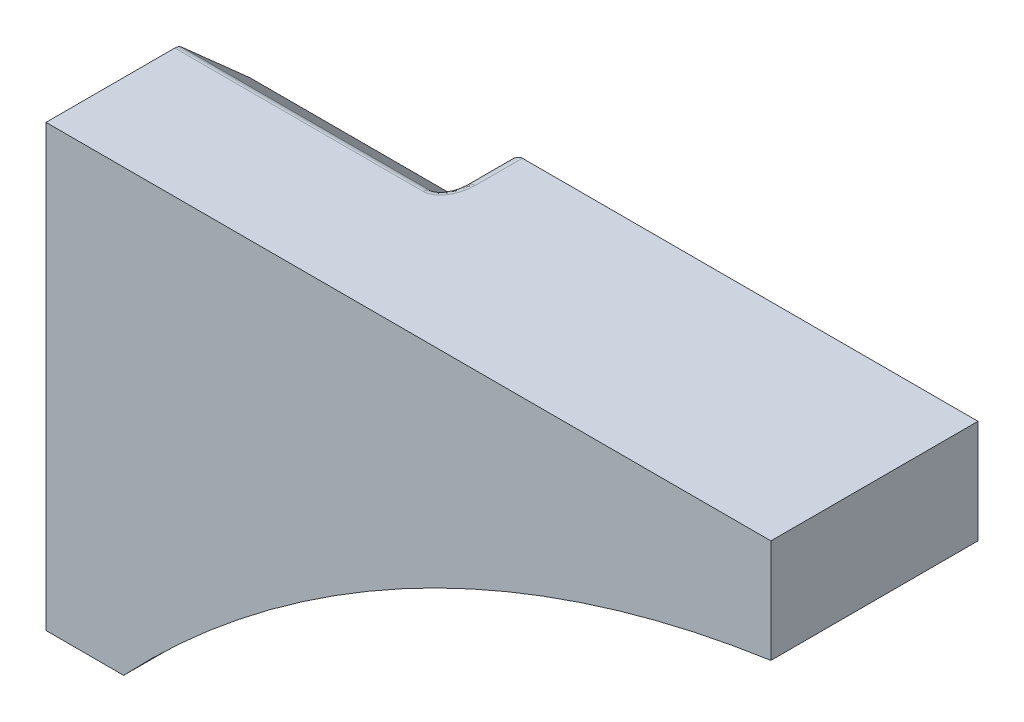
SolidWorks part; units mm, degrees
material "Nylon 101"
ref_plane "Front Plane" through (0, 0, 0) normal (0, 0, 1) x (1, 0, 0)
ref_plane "Top Plane" through (0, 0, 0) normal (0, 1, 0) x (1, 0, 0)
ref_plane "Right Plane" through (0, 0, 0) normal (1, 0, 0) x (0, 0, -1)
sketch "Sketch1" plane through (0, 0, 0) normal (0, 0, 1) x (1, 0, 0)
  line L0 (0, 0) -> (0, -107.95)
  line L2 (177.8, 0) -> (0, 0)
  line L3 (0, -107.95) -> (19.05, -107.95)
  line L5 (177.8, -25.4) -> (177.8, 0)
  line L6 (19.05, -107.95) -> (19.05, -25.4)
  line L7 (19.05, -25.4) -> (177.8, -25.4)
  dimension "D1" = 107.95
  dimension "D2" = 19.05
  dimension "D3" = 25.4
  dimension "D4" = 177.8
extrude "Boss-Extrude1" add sketch "Sketch1" along normal blind 50.8
sketch "Sketch2" plane through (0, 0, 0) normal (-1, 0, 0) x (0, 0, 1)
  line L0 (25.4, 0) -> (25.4, -107.95) construction
  line L1 (50.8, 0) -> (0, 0) construction
  line L2 (50.8, -107.95) -> (0, -107.95) construction
  point P6 (25.4, -31.75)
  point P7 (25.4, -88.9)
  dimension "D1" = 57.15
  dimension "0.5" = 19.05
hole_wizard "#8 Clearance Hole1" positions "Sketch3" profile "Sketch4" hole size "#8" standard "ANSI Inch" end condition through all
sketch "Sketch3" plane through (0, 0, 0) normal (-1, 0, 0) x (0, 0, 1)
  point P0 (25.4, -31.75)
  point P3 (25.4, -88.9)
sketch "Sketch4" plane through (0, -31.75, 25.4) normal (0, 1, 0) x (0, 0, 1)
  line L0 (0, 0) -> (0, 177.8)
  line L1 (0, 177.8) -> (2.2479, 177.8)
  line L2 (2.2479, 177.8) -> (2.2479, 0)
  line L5 (2.2479, 0) -> (0, 0)
  line L11 (0, -6.35) -> (0, 107.95) construction
  dimension "Thru Hole Dia." = 4.4958
  dimension "Thru Hole Depth" = 177.8
hole_wizard "CBORE for #8 Binding Head Machine Screw1" positions "Sketch5" profile "Sketch6" counterbore size "#8" standard "ANSI Inch" end condition through all
sketch "Sketch5" plane through (19.05, 0, 0) normal (1, 0, 0) x (0, 0, -1)
  point P0 (-25.4, -31.75)
  point P3 (-25.4, -88.9)
sketch "Sketch6" plane through (19.05, -31.75, 25.4) normal (0, 1, 0) x (0, 0, -1)
  line L0 (0, 0) -> (0, 19.05)
  line L1 (0, 19.05) -> (2.2479, 19.05)
  line L3 (2.2479, 19.05) -> (2.2479, 12.7)
  line L4 (2.2479, 12.7) -> (4.7625, 12.7)
  line L5 (4.7625, 12.7) -> (4.7625, 0)
  line L7 (4.7625, 0) -> (0, 0)
  line L11 (0, -6.35) -> (0, 107.95) construction
  dimension "Thru Hole Dia." = 4.4958
  dimension "Thru Hole Depth" = 19.05
  dimension "C'Bore Dia." = 9.525
  dimension "C'Bore Depth" = 12.7
sketch "Sketch7" plane through (0, 0, 50.8) normal (0, 0, 1) x (1, 0, 0)
  line L4 (19.05, -107.95) -> (19.05, -25.4)
  line L5 (19.05, -25.4) -> (177.8, -25.4)
  line L6 (19.05, -25.4) -> (177.8, -25.4) construction
  arc A1 (19.05, -107.95) -> (177.8, -25.4) centre (216.7199, -294.1652) cw
extrude "Boss-Extrude2" add sketch "Sketch7" against normal blind 7.62
ref_plane "Plane1" through (0, 0, 25.4) normal (0, 0, -1) x (-1, 0, 0)
mirror "Mirror1" about plane through (0, 0, 25.4) normal (0, 0, -1) of "Boss-Extrude2"
sketch "Sketch8" plane through (0, 0, 0) normal (-1, 0, 0) x (0, 0, 1)
  line L0 (18.2524, 0) -> (0, -16.2128)
  line L1 (50.8, 0) -> (0, 0) construction
  line L2 (0, 0) -> (0, -107.95) construction
  line L3 (0, -16.2128) -> (0, 0)
  line L4 (0, 0) -> (18.2524, 0)
  dimension "D1" = 18.2524
  dimension "D2" = 16.2128
extrude "Cut-Extrude1" cut sketch "Sketch8" against normal blind 63.5
fillet "Fillet1" radius 2.54 5 edges at (31.75, -16.2128, 0) (31.75, 0, 18.2524) (63.5, -8.1064, 0) (63.5, 0, 9.1262) (63.5, -8.1064, 9.1262)
